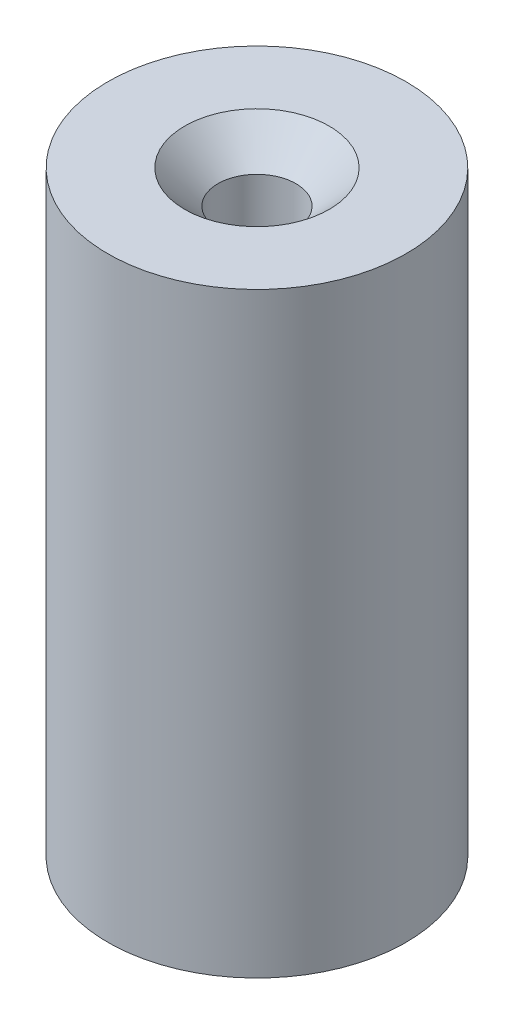
SolidWorks part; units mm, degrees
material "Сплав 2024"
ref_plane "Спереди" through (0, 0, 0) normal (0, 0, 1) x (1, 0, 0)
ref_plane "Сверху" through (0, 0, 0) normal (0, 1, 0) x (1, 0, 0)
ref_plane "Справа" through (0, 0, 0) normal (1, 0, 0) x (0, 0, -1)
sketch "Эскиз1" plane through (0, 0, 0) normal (0, 1, 0) x (1, 0, 0)
  circle A0 centre (0, 0) radius 6.5
  dimension "D1" = 13
extrude "Бобышка-Вытянуть1" add sketch "Эскиз1" along normal blind 26
sketch "Эскиз2" plane through (0, 0, 0) normal (0, -1, 0) x (1, 0, 0)
  circle A0 centre (0, 0) radius 2.85
  dimension "D1" = 5.7
extrude "Вырез-Вытянуть1" cut sketch "Эскиз2" against normal blind 3.5
hole_wizard "Зенковка для  винта с плоской головкой M32" positions "Эскиз4" profile "Эскиз3" countersink size "M3" standard "Ansi Metric" end condition through all
sketch "Эскиз4" plane through (0, 26, 0) normal (0, 1, 0) x (1, 0, 0)
  point P0 (0, 0)
sketch "Эскиз3" plane through (0, 26, 0) normal (1, 0, 0) x (0, 0, 1)
  line L0 (0, 0) -> (0, 26)
  line L1 (0, 26) -> (1.7, 26)
  line L2 (1.7, 26) -> (1.7, 1.45)
  line L3 (1.7, 1.45) -> (3.15, 0)
  line L5 (3.15, 0) -> (0, 0)
  line L6 (-1.7, 1.45) -> (-3.15, 0) construction
  line L11 (0, -6.35) -> (0, 107.95) construction
  dimension "Диаметр сквозного отверстия" = 3.4
  dimension "Глубина сквозного отверстия" = 26
  dimension "Диаметр передней зенковки" = 6.3
  dimension "Угол передней зенковки" = 90
